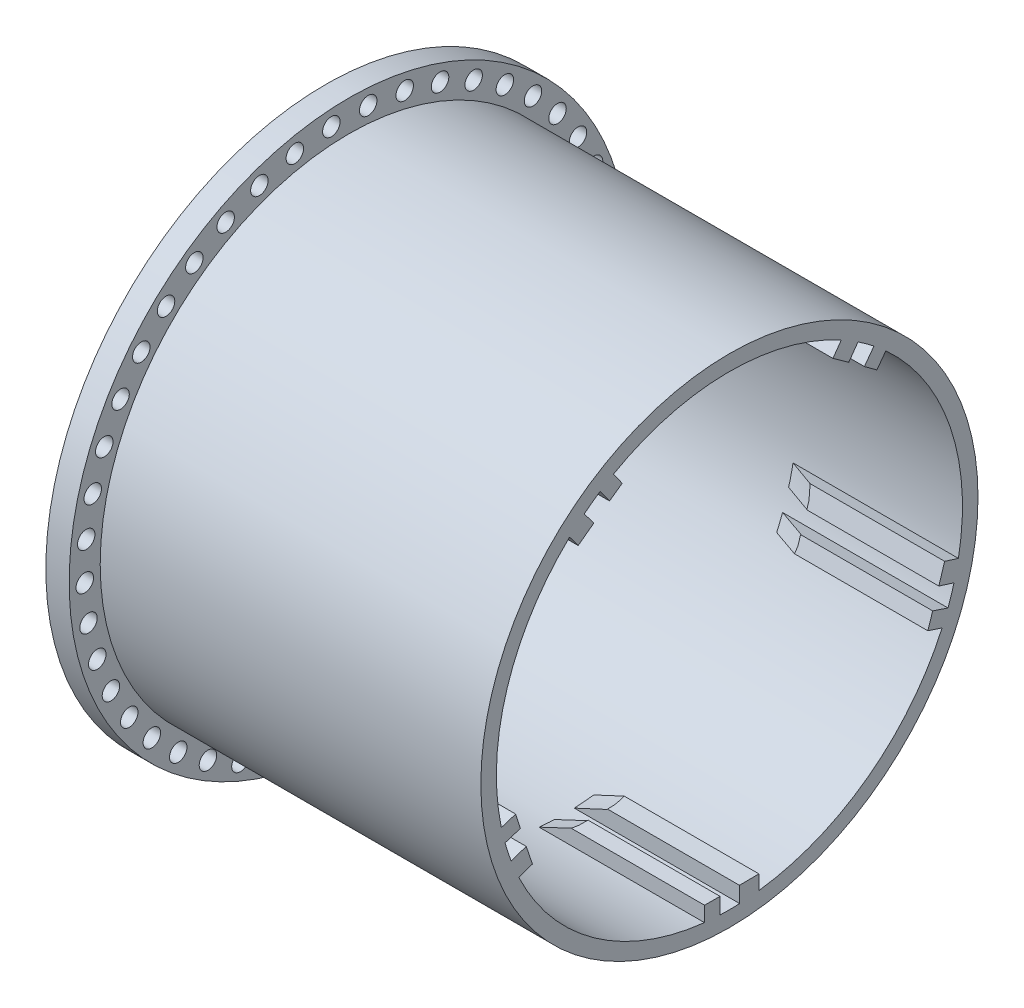
SolidWorks part; units mm, degrees
material "ABS"
ref_plane "Front Plane" through (0, 0, 0) normal (0, 0, 1) x (1, 0, 0)
ref_plane "Top Plane" through (0, 0, 0) normal (0, 1, 0) x (1, 0, 0)
ref_plane "Right Plane" through (0, 0, 0) normal (1, 0, 0) x (0, 0, -1)
sketch "Sketch1" plane through (0, 0, 0) normal (1, 0, 0) x (0, 0, -1)
  line L0 (0, 0) -> (20.089, 27.4305) construction
  line L1 (-2, 1.5) -> (2, 1.5)
  line L3 (-2, -1.5) -> (2, -1.5)
  line L5 (-2, 1.5) -> (2, -1.5) construction
  line L6 (-2, -1.5) -> (2, 1.5) construction
  circle A0 centre (0, 0) radius 30
  arc A1 (-2, 1.5) -> (-2, -1.5) centre (0, 0) ccw
  arc A2 (2, -1.5) -> (2, 1.5) centre (0, 0) ccw
  circle A3 centre (20.089, 27.4305) radius 1.125
  circle A4 centre (23.7111, 24.3677) radius 1.125
  circle A5 centre (26.8717, 20.8306) radius 1.125
  circle A6 centre (29.5092, 16.888) radius 1.125
  circle A7 centre (31.5724, 12.6168) radius 1.125
  circle A8 centre (33.0211, 8.1) radius 1.125
  circle A9 centre (33.827, 3.4255) radius 1.125
  circle A10 centre (33.9745, -1.3156) radius 1.125
  circle A11 centre (33.4608, -6.0312) radius 1.125
  circle A12 centre (32.2958, -10.6293) radius 1.125
  circle A13 centre (30.5022, -15.0206) radius 1.125
  circle A14 centre (28.1149, -19.1195) radius 1.125
  circle A15 centre (25.1803, -22.8463) radius 1.125
  circle A16 centre (21.7557, -26.1283) radius 1.125
  circle A17 centre (17.9076, -28.9019) radius 1.125
  circle A18 centre (13.711, -31.1129) radius 1.125
  circle A19 centre (9.2475, -32.7183) radius 1.125
  circle A20 centre (4.604, -33.6868) radius 1.125
  circle A21 centre (-0.1292, -33.9998) radius 1.125
  circle A22 centre (-4.8597, -33.6509) radius 1.125
  circle A23 centre (-9.4957, -32.6471) radius 1.125
  circle A24 centre (-13.9469, -31.0078) radius 1.125
  circle A25 centre (-18.1267, -28.765) radius 1.125
  circle A26 centre (-21.9536, -25.9623) radius 1.125
  circle A27 centre (-25.3532, -22.6543) radius 1.125
  circle A28 centre (-28.2593, -18.9054) radius 1.125
  circle A29 centre (-30.6154, -14.7884) radius 1.125
  circle A30 centre (-32.3756, -10.3837) radius 1.125
  circle A31 centre (-33.5056, -5.7768) radius 1.125
  circle A32 centre (-33.9836, -1.0575) radius 1.125
  circle A33 centre (-33.8, 3.6824) radius 1.125
  circle A34 centre (-32.9586, 8.3506) radius 1.125
  circle A35 centre (-31.4756, 12.8563) radius 1.125
  circle A36 centre (-29.3801, 17.1117) radius 1.125
  circle A37 centre (-26.7127, 21.0341) radius 1.125
  circle A38 centre (-23.5253, 24.5471) radius 1.125
  circle A39 centre (-19.8801, 27.5823) radius 1.125
  circle A40 centre (-15.8479, 30.0806) radius 1.125
  circle A41 centre (-11.5072, 31.9935) radius 1.125
  circle A42 centre (-6.9426, 33.2836) radius 1.125
  circle A43 centre (-2.2429, 33.9259) radius 1.125
  circle A44 centre (2.5005, 33.9079) radius 1.125
  circle A45 centre (7.1953, 33.2299) radius 1.125
  circle A46 centre (11.75, 31.9051) radius 1.125
  circle A47 centre (16.076, 29.9594) radius 1.125
  circle A48 centre (0, 0) radius 4.25
  circle A49 centre (0, 0) radius 36
  circle A50 centre (0, 0) radius 32
  dimension "D1" = 60
  dimension "D4" = 2.25
  dimension "D7" = 8.5
  dimension "D8" = 72
  dimension "D2" = 4
  dimension "D3" = 3
  dimension "D5" = 34
  dimension "D9" = 2
  dimension "D6" = 45
extrude "Boss-Extrude1" add sketch "Sketch1" along normal blind 3 contours A0 A48 | A50 A0 | A49 A50 A3 A4 A5 A6 A7 A8 A9 A10 A11 A12 A13 A14 A15 A16 A17 A18 A19 A20 A21 A22 A23 A24 A25 A26 region at (0, 0, 29.1515) region at (0, 0, 34.9818) region at (0, 0, 31.0949)
sketch "Sketch2" plane through (3, 0, 0) normal (1, 0, 0) x (0, 0, -1)
  line L0 (-26.1553, -9.8616) -> (-28.0974, -10.5135)
  line L1 (-1.2034, -27.9057) -> (-1.2173, -29.9753)
  line L2 (1.2965, -27.9225) -> (1.3164, -29.9711)
  line L3 (-26.9118, -7.4788) -> (-28.8844, -8.1051)
  line L4 (-17.4614, 21.8277) -> (-18.6815, 23.4734)
  line L5 (-15.429, 23.2835) -> (-16.6342, 24.9661)
  line L6 (15.3635, 23.3519) -> (16.5516, 25.0209)
  line L7 (17.3761, 21.8688) -> (18.6039, 23.535)
  line L8 (26.9566, -7.3954) -> (28.911, -8.0096)
  line L9 (26.168, -9.7678) -> (28.132, -10.4206)
  line L11 (-27.517, -5.5726) -> (-29.3612, -6.1581)
  line L13 (-26.1553, -9.8616) -> (-28.1279, -10.4879)
  line L14 (-25.3597, -12.2317) -> (-27.1214, -12.823)
  line L15 (-26.9118, -7.4788) -> (-27.517, -5.5726)
  line L16 (-26.1553, -9.8616) -> (-25.3597, -12.2317)
  line L17 (-25.3597, -12.2317) -> (-27.3019, -12.8836) construction
  line L18 (-27.517, -5.5726) -> (-29.4896, -6.1989) construction
  line L19 (-13.8031, 24.4482) -> (-14.9298, 26.0212)
  line L20 (-15.429, 23.2835) -> (-13.8031, 24.4482)
  line L21 (-15.429, 23.2835) -> (-16.6342, 24.9661)
  line L22 (-17.4614, 21.8277) -> (-18.6815, 23.4734)
  line L23 (-17.4614, 21.8277) -> (-19.4696, 20.3387)
  line L24 (-19.4696, 20.3387) -> (-20.5764, 21.8315)
  line L25 (18.9862, 20.6824) -> (20.134, 22.2401)
  line L26 (17.3761, 21.8688) -> (18.9862, 20.6824)
  line L27 (17.3761, 21.8688) -> (18.6039, 23.535)
  line L28 (15.3635, 23.3519) -> (16.5516, 25.0209)
  line L29 (15.3635, 23.3519) -> (13.3269, 24.8017)
  line L30 (13.3269, 24.8017) -> (14.4045, 26.3156)
  line L31 (25.5372, -11.6657) -> (27.3733, -12.276)
  line L32 (26.168, -9.7678) -> (25.5372, -11.6657)
  line L33 (26.168, -9.7678) -> (28.132, -10.4206)
  line L34 (26.9566, -7.3954) -> (28.911, -8.0096)
  line L35 (26.9566, -7.3954) -> (27.7061, -5.0104)
  line L36 (27.7061, -5.0104) -> (29.4788, -5.5676)
  line L37 (-3.2034, -27.8922) -> (-3.2164, -29.8271)
  line L38 (-1.2034, -27.9057) -> (-3.2034, -27.8922)
  line L39 (-1.2034, -27.9057) -> (-1.2173, -29.9753)
  line L40 (1.2965, -27.9225) -> (1.3164, -29.9711)
  line L41 (1.2965, -27.9225) -> (3.7964, -27.8983)
  line L42 (3.7964, -27.8983) -> (3.8144, -29.7565)
  circle A2 centre (0, 0) radius 30 construction
  arc A3 (-1.2173, -29.9753) -> (1.3164, -29.9711) centre (0, 0) ccw
  arc A5 (-28.8844, -8.1051) -> (-28.0974, -10.5135) centre (0, 0) ccw
  arc A7 (-16.6342, 24.9661) -> (-18.6815, 23.4734) centre (0, 0) ccw
  arc A9 (18.6039, 23.535) -> (16.5516, 25.0209) centre (0, 0) ccw
  arc A11 (28.132, -10.4206) -> (28.911, -8.0096) centre (0, 0) ccw
  arc A12 (-28.8844, -8.1051) -> (-28.0974, -10.5135) centre (0, 0) ccw
  circle A13 centre (0, 0) radius 32 construction
  circle A14 centre (0, 0) radius 32
  arc A15 (-27.1214, -12.823) -> (-3.2164, -29.8271) centre (0, 0) ccw
  arc A20 (28.132, -10.4206) -> (28.911, -8.0096) centre (0, 0) ccw
  arc A21 (29.4788, -5.5676) -> (20.134, 22.2401) centre (0, 0) ccw
  arc A22 (14.4045, 26.3156) -> (-14.9298, 26.0212) centre (0, 0) ccw
  arc A23 (18.6039, 23.535) -> (16.5516, 25.0209) centre (0, 0) ccw
  arc A24 (-20.5764, 21.8315) -> (-29.3612, -6.1581) centre (0, 0) ccw
  arc A25 (-16.6342, 24.9661) -> (-18.6815, 23.4734) centre (0, 0) ccw
  arc A26 (-1.2173, -29.9753) -> (1.3164, -29.9711) centre (0, 0) ccw
  arc A27 (3.8144, -29.7565) -> (27.3733, -12.276) centre (0, 0) ccw
  dimension "D2" = 2
  dimension "D1" = 5
  dimension "D3" = 2.5
  dimension "D4" = 5
extrude "Boss-Extrude4" add sketch "Sketch2" along normal blind 49 contours A14 A27 L42 L41 L2 A3 L1 L38 L37 A15 L14 L16 L0 A5 L3 L15 L11 A24 L24 L23 L4 A7 L5 L20 L19 A22 L30 L29 L6 A9 L7 L26 L25 A21 L36 L35 L8 A11 L9 L32 L31 region at (3, 0, 31.0949)
extrude "Cut-Extrude3" cut sketch "Sketch1<7>" along normal blind 3 contours A0
sketch "Sketch1<7>" plane through (0, 0, 0) normal (1, 0, 0) x (0, 0, -1) same geometry as "Sketch1"
sketch "Sketch3" plane through (52, 0, 0) normal (1, 0, 0) x (0, 0, -1)
  circle A2 centre (0, 0) radius 30
  circle A3 centre (0, 0) radius 30
  dimension "D1" = 2
extrude "Cut-Extrude4" cut sketch "Sketch3" against normal through all from offset 17 offset against normal yes
chamfer "Chamfer1" [suppressed] distance 2 angle 60
chamfer "Chamfer2" distance 2 angle 65 10 edges at (35, 25.5078, 15.7908) (35, 22.9003, -19.3798) (35, 25.6907, -15.4916) (35, -6.7945, -29.2204) (35, -11.3547, -27.7682) (35, -29.8899, -2.5676) (35, -29.9179, 2.2181) (35, -7.1356, 29.139) (35, -11.6785, 27.6336) (35, 22.6722, 19.6461) first distance on face at (35, 24.6833, 15.2012) first distance on face at (35, 22.0848, -18.7778) first distance on face at (35, 24.8781, -14.915) first distance on face at (35, -6.4973, -28.2695) first distance on face at (35, -11.0341, -26.8065) first distance on face at (35, -28.8937, -2.5565) first distance on face at (35, -28.9042, 2.2104) first distance on face at (35, -6.8297, 28.1726) first distance on face at (35, -11.36, 26.6895) first distance on face at (35, 21.8728, 19.0515)
